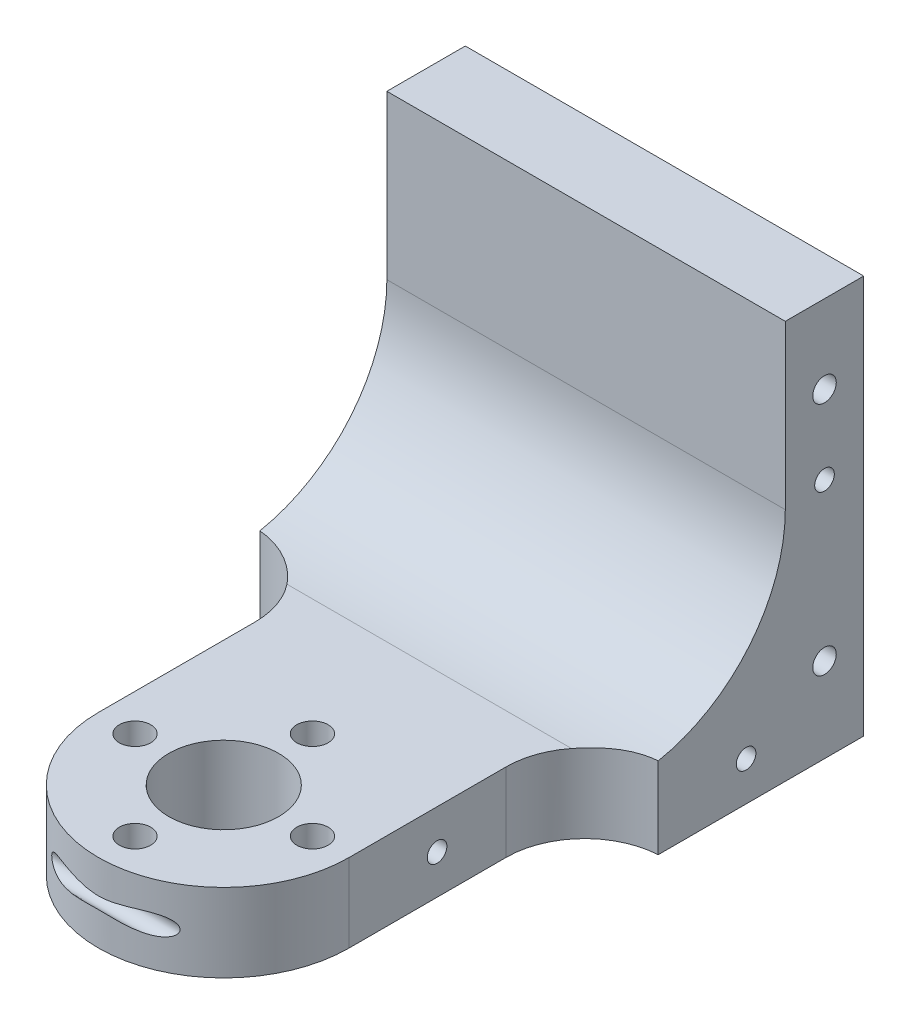
SolidWorks part; units mm, degrees
ref_plane "Front" through (0, 0, 0) normal (0, 0, 1) x (1, 0, 0)
ref_plane "Top" through (0, 0, 0) normal (0, 1, 0) x (1, 0, 0)
ref_plane "Right" through (0, 0, 0) normal (1, 0, 0) x (0, 0, -1)
sketch "Sketch1" plane through (0, 0, 0) normal (0, 1, 0) x (1, 0, 0)
  line L0 (25.4, 0) -> (25.4, 20)
  line L1 (0, 0) -> (50.8, 0)
  line L2 (0, 0) -> (0, 66.2)
  line L3 (0, 66.2) -> (50.8, 66.2)
  line L4 (50.8, 0) -> (50.8, 66.2)
  circle A0 centre (25.4, 20) radius 11.3137
  circle A1 centre (14.0863, 20) radius 2
  circle A2 centre (25.4, 8.6863) radius 2
  circle A3 centre (36.7137, 20) radius 2
  circle A4 centre (25.4, 31.3137) radius 2
  circle A5 centre (25.4, 20) radius 7
  dimension "D1" = 50.8
  dimension "D2" = 66.2
  dimension "D3" = 20
extrude "Boss-Extrude1" add sketch "Sketch1" along normal blind 10 contours A4 A0 A3 A2 L1 L4 L3 L2 A1 | A4 A0 A1 A2 A3 region at (25.4, 0, -35.0114) region at (17.6227, 0, -12.2227)
sketch "Sketch2" plane through (0, 0, -66.2) normal (0, 0, -1) x (-1, 0, 0)
  line L1 (-50.8, 0) -> (0, 0)
  line L2 (-50.8, 0) -> (-50.8, 50.8)
  line L3 (-50.8, 50.8) -> (0, 50.8)
  line L4 (0, 0) -> (0, 50.8)
  dimension "D1" = 50.8
extrude "Boss-Extrude2" add sketch "Sketch2" along normal blind 10
fillet "Fillet2" radius 20 1 edges at (25.4, 10, -66.2)
sketch "Sketch3" plane through (50.8, 0, 0) normal (1, 0, 0) x (0, 0, -1)
  line L0 (0, 5) -> (5, 5)
  line L1 (0, 10) -> (0, 0) construction
  line L2 (76.2, 50.8) -> (76.2, 0) construction
  circle A0 centre (61.2, 5) radius 1.25
  circle A1 centre (31.2, 5) radius 1.25
  circle A2 centre (5, 5) radius 1.25
  dimension "D1" = 45
  dimension "D2" = 15
  dimension "D3" = 5
extrude "Cut-Extrude1" cut sketch "Sketch3" against normal through all contours A1 | A0 | A2
sketch "Sketch4" plane through (50.8, 0, 0) normal (1, 0, 0) x (0, 0, -1)
  line L0 (71.2, 50.8) -> (71.2, 30.8)
  line L1 (76.2, 50.8) -> (66.2, 50.8) construction
  line L2 (71.2, 30.8) -> (71.2, -9.2)
  circle A0 centre (71.2, -9.2) radius 1.25
  circle A1 centre (71.2, 30.8) radius 1.25
  circle A2 centre (71.2, 10.8) radius 1.5
  circle A3 centre (71.2, 40.8) radius 1.5
  dimension "D1" = 20
  dimension "D2" = 40
extrude "Cut-Extrude2" cut sketch "Sketch4" against normal through all contours A1 | A0 | A2 | A3
sketch "Sketch5" plane through (0, 0, 0) normal (0, -1, 0) x (-1, 0, 0)
  line L0 (-25.4, 20) -> (-25.4, 4)
  line L1 (-41.4, 20) -> (-41.4, 50)
  line L2 (-41.4, 50) -> (-9.4, 50)
  line L3 (-9.4, 50) -> (-9.4, 20)
  line L4 (-41.4, 50) -> (-50.8, 50)
  line L5 (-50.8, 0) -> (-50.8, 76.2) construction
  line L6 (-50.8, 50) -> (-50.8, 0)
  line L7 (-50.8, 0) -> (0, 0)
  line L8 (0, 0) -> (0, 50)
  line L9 (0, 0) -> (0, 76.2) construction
  line L10 (0, 50) -> (-9.4, 50)
  arc A0 (-41.4, 20) -> (-9.4, 20) centre (-25.4, 20) ccw
  line M7 (0, 0) -> (0, 76.2)
  line M9 (-50.8, 76.2) -> (-50.8, 0)
  line M10 (-50.8, 0) -> (0, 0)
  dimension "D2" = 30
  dimension "D1" = 16
extrude "Cut-Extrude3" cut sketch "Sketch5" against normal through all contours A0 L1 L4 L10 L3 M9 M10 M7 region at (37.2177, 0, -8.1823)
fillet "Fillet3" radius 10 2 edges at (9.4, 5.1822, -50) (41.4, 5.1822, -50)
